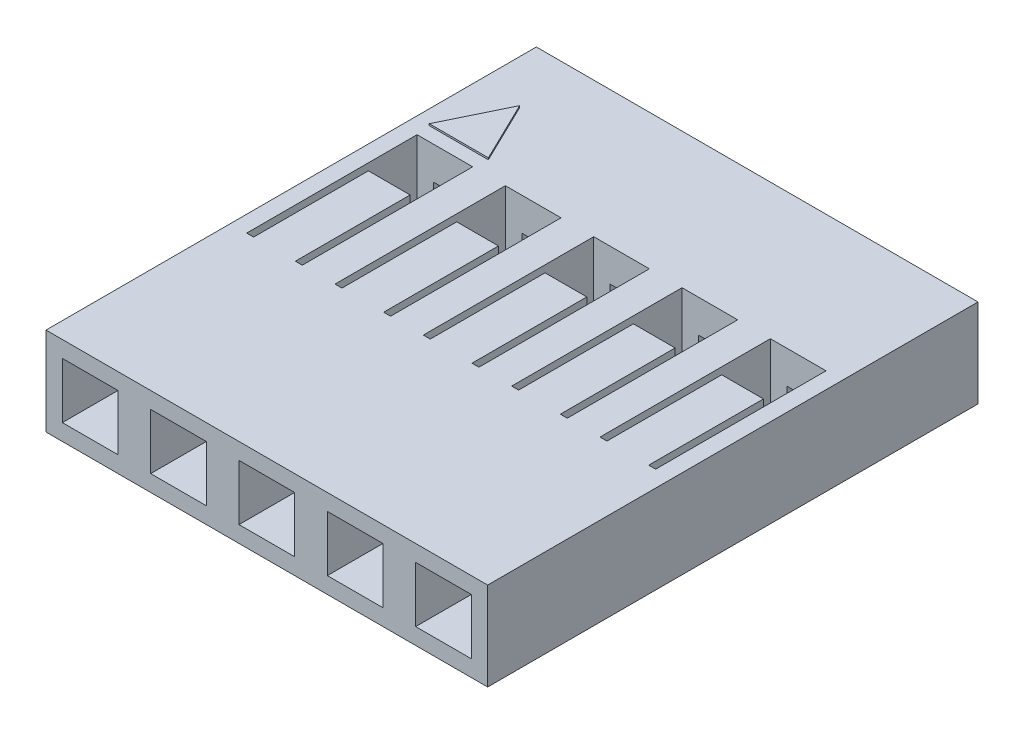
SolidWorks part; units mm, degrees
ref_plane "Front Plane" through (0, 0, 0) normal (0, 0, 1) x (1, 0, 0)
ref_plane "Top Plane" through (0, 0, 0) normal (0, 1, 0) x (1, 0, 0)
ref_plane "Right Plane" through (0, 0, 0) normal (1, 0, 0) x (0, 0, -1)
sketch "Sketch1" plane through (0, 0, 0) normal (0, 0, 1) x (1, 0, 0)
  line L0 (0, 0) -> (0, 2.54)
  line L1 (0, 2.54) -> (2.54, 2.54)
  line L2 (2.54, 2.54) -> (2.54, 0)
  line L3 (2.54, 0) -> (0, 0)
  line L4 (1.27, 2.54) -> (1.27, 0) construction
  line L5 (0, 1.27) -> (2.54, 1.27) construction
  line L7 (0.945, 0.945) -> (1.595, 0.945)
  line L8 (0.945, 0.945) -> (0.945, 1.595)
  line L9 (0.945, 1.595) -> (1.595, 1.595)
  line L10 (1.595, 0.945) -> (1.595, 1.595)
  line L11 (0.945, 0.945) -> (1.595, 1.595) construction
  line L12 (0.945, 1.595) -> (1.595, 0.945) construction
  point P9 (1.27, 1.27)
  dimension "D1" = 2.54
  dimension "D2" = 0.65
extrude "Boss-Extrude1" add sketch "Sketch1" along normal blind 14.1
chamfer "Chamfer1" distance 0.5 angle 45 4 edges at (1.27, 0.945, 0) (0.945, 1.27, 0) (1.595, 1.27, 0) (1.27, 1.595, 0)
sketch "Sketch4" plane through (0, 2.54, 0) normal (0, 1, 0) x (1, 0, 0)
  line L0 (1.27, 0) -> (1.27, -14.1) construction
  line L1 (2.54, 0) -> (0, 0) construction
  line L2 (2.54, -14.1) -> (0, -14.1) construction
  line L4 (2.07, -5.5) -> (0.47, -5.5)
  line L5 (2.07, -5.5) -> (2.07, -3.9)
  line L6 (2.07, -3.9) -> (0.47, -3.9)
  line L7 (0.47, -5.5) -> (0.47, -3.9)
  line L8 (2.07, -5.5) -> (0.47, -3.9) construction
  line L9 (2.07, -3.9) -> (0.47, -5.5) construction
  point P6 (1.27, -4.7)
  dimension "D1" = 1.6
  dimension "D2" = 3.9
extrude "Cut-Extrude2" cut sketch "Sketch4" against normal blind 1.5
sketch "Sketch2" plane through (0, 0, 14.1) normal (0, 0, 1) x (1, 0, 0)
  line L8 (0.47, 0.47) -> (2.07, 0.47)
  line L9 (2.07, 0.47) -> (2.07, 2.07)
  line L10 (0.47, 2.07) -> (0.47, 0.47)
  line L11 (2.07, 2.07) -> (0.47, 2.07)
  line L12 (0.47, 0.47) -> (2.07, 0.47)
  line L13 (2.07, 0.47) -> (2.07, 2.07)
  line L14 (0.47, 2.07) -> (0.47, 0.47)
  line L15 (2.07, 2.07) -> (0.47, 2.07)
  dimension "D1" = 0.475
extrude "Cut-Extrude1" cut sketch "Sketch2" against normal up to surface (10.2 mm away) up to face at (1.27, 1.5537, 3.9)
sketch "Sketch3" plane through (0, 2.54, 0) normal (0, 1, 0) x (1, 0, 0)
  line L0 (0, -3.5) -> (2.54, -3.5) construction
  line L1 (0, -14.1) -> (0, 0) construction
  line L2 (2.54, -14.1) -> (2.54, 0) construction
  line L3 (2.54, 0) -> (0, 0) construction
  line L4 (1.27, -3.5) -> (1.27, 0) construction
  line L5 (2.12, -3.5) -> (0.42, -3.5)
  line L6 (0.42, -3.5) -> (1.27, -1.75)
  line L7 (2.12, -3.5) -> (1.27, -1.75)
  dimension "D1" = 3.5
  dimension "D2" = 1.7
extrude "Boss-Extrude2" add sketch "Sketch3" along normal blind 0.05
sketch "Sketch5" plane through (0, 2.54, 0) normal (0, 1, 0) x (1, 0, 0)
  line L0 (1.27, 0) -> (1.27, -14.1) construction
  line L1 (2.54, 0) -> (0, 0) construction
  line L2 (2.54, -14.1) -> (0, -14.1) construction
  line L3 (0.47, -5.5) -> (0.47, -8.8)
  line L4 (0.47, -5.5) -> (2.07, -5.5) construction
  line L5 (0.47, -8.8) -> (0.67, -8.8)
  line L6 (0.67, -8.8) -> (0.67, -5.5)
  line L7 (0.67, -5.5) -> (0.47, -5.5)
  line L8 (0.47, -3.9) -> (0.47, -14.1) construction
  line L9 (1.87, -8.8) -> (1.87, -5.5)
  line L10 (2.07, -8.8) -> (1.87, -8.8)
  line L11 (2.07, -5.5) -> (2.07, -8.8)
  line L12 (1.87, -5.5) -> (2.07, -5.5)
  dimension "D1" = 0.6
  dimension "D2" = 3.3
extrude "Cut-Extrude3" cut sketch "Sketch5" against normal up to surface (0.47 mm away) up to face at (1.27, 2.07, 9.8)
pattern_linear "LPattern1" count 5 spacing 2.54 along (1, 0, 0) of "Boss-Extrude1", "Cut-Extrude1", "Cut-Extrude2", "Cut-Extrude3", "Chamfer1"
